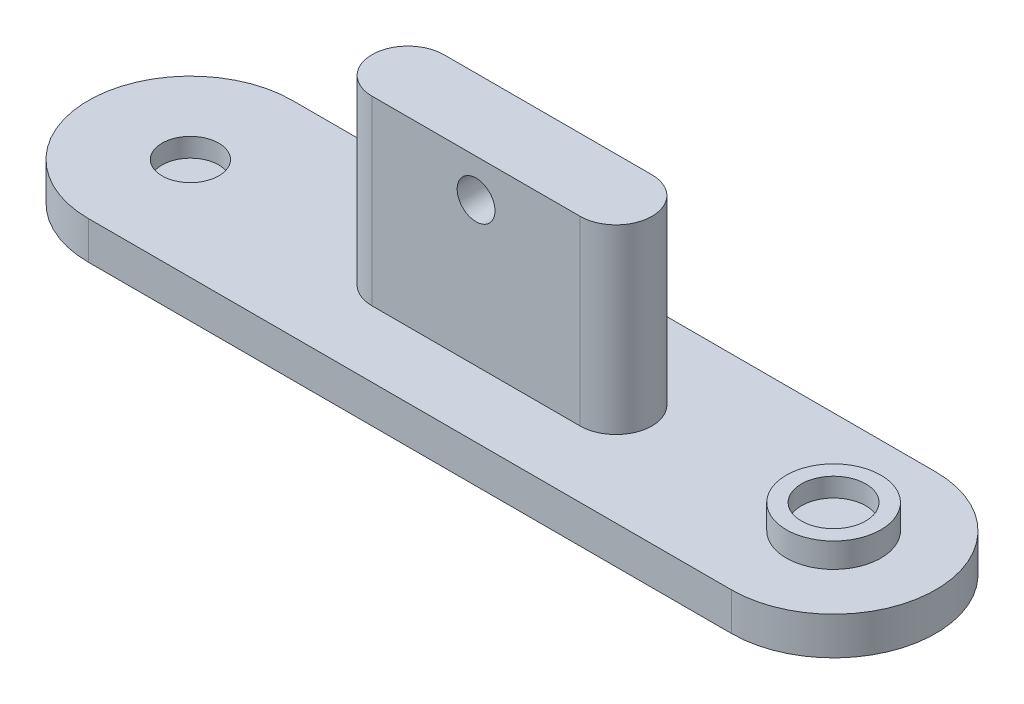
SolidWorks part; units mm, degrees
ref_plane "Front Plane" through (0, 0, 0) normal (0, 0, 1) x (1, 0, 0)
ref_plane "Top Plane" through (0, 0, 0) normal (0, 1, 0) x (1, 0, 0)
ref_plane "Right Plane" through (0, 0, 0) normal (1, 0, 0) x (0, 0, -1)
sketch "Sketch1" plane through (0, 0, 0) normal (0, 1, 0) x (1, 0, 0)
  line L0 (-142.4958, 0) -> (136.0591, 0) construction
  line L1 (0, 82.9006) -> (0, -67.1417) construction
  line L2 (-42.5, -13.5) -> (42.5, -13.5)
  line L3 (-42.5, 13.5) -> (42.5, 13.5)
  arc A0 (-42.5, 13.5) -> (-42.5, -13.5) centre (-42.5, 0) ccw
  arc A1 (42.5, 13.5) -> (42.5, -13.5) centre (42.5, 0) cw
  dimension "D1" = 85
  dimension "D2" = 27
extrude "Boss-Extrude1" add sketch "Sketch1" along normal blind 5
sketch "Sketch2" plane through (0, 5, 0) normal (0, 1, 0) x (1, 0, 0)
  circle A0 centre (-42.5, 0) radius 3.75
  arc A1 (-42.5, 13.5) -> (-42.5, -13.5) centre (-42.5, 0) ccw construction
  dimension "D1" = 7.5
extrude "Cut-Extrude1" cut sketch "Sketch2" against normal blind 2.5
sketch "Sketch3" plane through (0, 5, 0) normal (0, 1, 0) x (1, 0, 0)
  circle A0 centre (42.5, 0) radius 6.25
  arc A1 (42.5, -13.5) -> (42.5, 13.5) centre (42.5, 0) ccw construction
  dimension "D1" = 12.5
extrude "Boss-Extrude3" add sketch "Sketch3" along normal blind 3.25
sketch "Sketch4" plane through (0, 8.25, 0) normal (0, 1, 0) x (1, 0, 0)
  circle A0 centre (42.5, 0) radius 4.25
  circle A1 centre (42.5, 0) radius 6.25 construction
  dimension "D1" = 8.5
extrude "Cut-Extrude2" cut sketch "Sketch4" against normal blind 2.5
sketch "Sketch5" plane through (0, 5, 0) normal (0, 1, 0) x (1, 0, 0)
  line L0 (0, 28.1167) -> (0, -35.5844) construction
  line L1 (-13.75, 4.75) -> (13.75, 4.75)
  line L2 (-13.75, -4.75) -> (13.75, -4.75)
  arc A0 (-13.75, 4.75) -> (-13.75, -4.75) centre (-13.75, 0) ccw
  arc A1 (13.75, 4.75) -> (13.75, -4.75) centre (13.75, 0) cw
  dimension "D1" = 27.5
  dimension "D2" = 9.5
extrude "Boss-Extrude4" add sketch "Sketch5" along normal blind 24
sketch "Sketch6" plane through (0, 0, -4.75) normal (0, 0, -1) x (-1, 0, 0)
  line L2 (-13.75, 29) -> (13.75, 29) construction
  line L3 (0, -7.6238) -> (0, 35.8367) construction
  circle A0 centre (0, 24) radius 2.5
  dimension "D1" = 5
  dimension "D2" = 5
extrude "Cut-Extrude3" cut sketch "Sketch6" against normal through all
